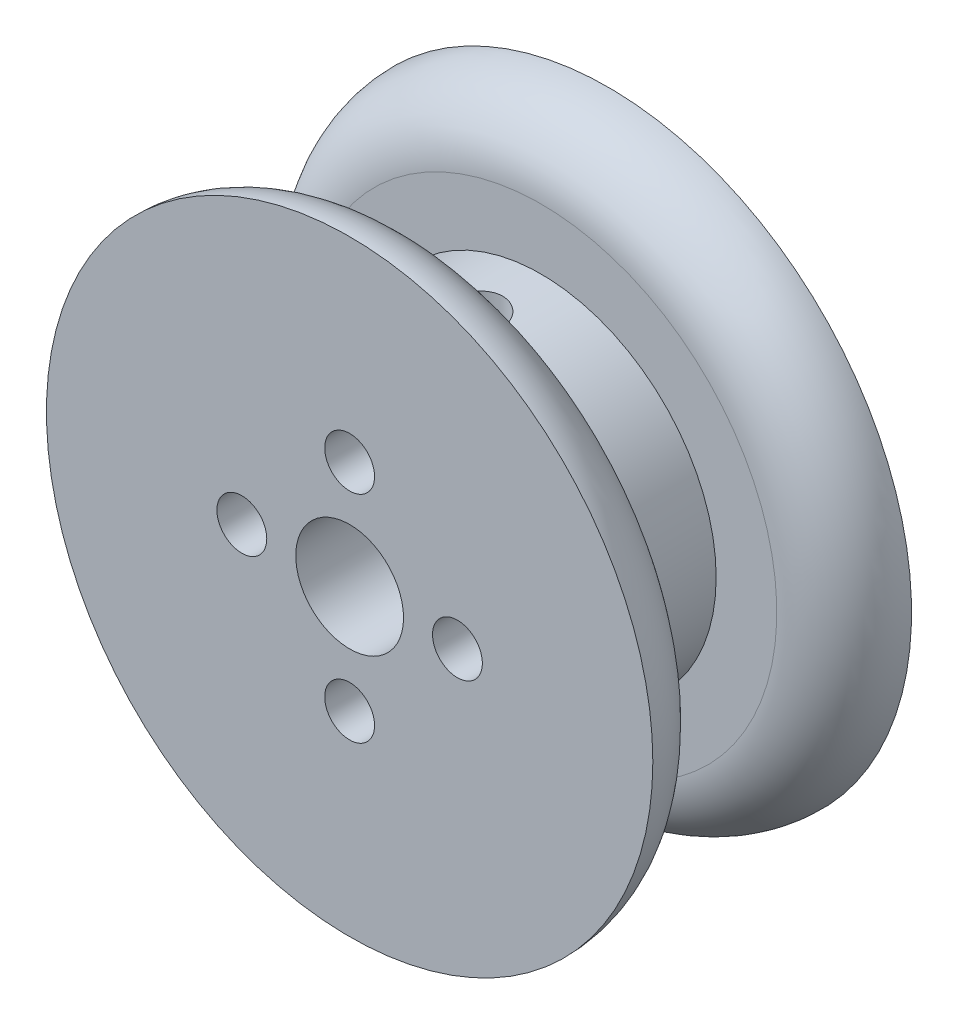
SolidWorks part; units mm, degrees
ref_plane "Front Plane" through (0, 0, 0) normal (0, 0, 1) x (1, 0, 0)
ref_plane "Top Plane" through (0, 0, 0) normal (0, 1, 0) x (1, 0, 0)
ref_plane "Right Plane" through (0, 0, 0) normal (1, 0, 0) x (0, 0, -1)
sketch "Sketch1" plane through (0, 0, 0) normal (0, 0, 1) x (1, 0, 0)
  circle A5 centre (0, 0) radius 22.5
  dimension "D1" = 45
extrude "Boss-Extrude1" add sketch "Sketch1" along normal blind 5
sketch "Sketch2" plane through (0, 0, 0) normal (0, 0, 1) x (1, 0, 0)
  circle A0 centre (0, 0) radius 13
  dimension "D1" = 26
extrude "Boss-Extrude2" add sketch "Sketch2" against normal blind 9.2
sketch "Sketch5" plane through (0, 0, -9.2) normal (0, 0, -1) x (-1, 0, 0)
  circle A2 centre (0, 0) radius 22.5
  circle A3 centre (0, 0) radius 22.5
  dimension "D1" = 0
extrude "Boss-Extrude4" add sketch "Sketch5" along normal blind 5
sketch "Sketch6" plane through (0, 0, 5) normal (0, 0, 1) x (1, 0, 0)
  line L0 (0, 0) -> (0, 8) construction
  circle A0 centre (0, 0) radius 4
  circle A1 centre (0, 8) radius 1.85
  circle A2 centre (8, 0) radius 1.85
  circle A3 centre (0, -8) radius 1.85
  circle A4 centre (-8, 0) radius 1.85
  point P14 (0, 0)
  dimension "D1" = 8
  dimension "D3" = 3.7
  dimension "D2" = 8
  dimension "D4" = 4
extrude "Cut-Extrude1" cut sketch "Sketch6" against normal through all
fillet "Fillet1" radius 5 2 edges at (22.5, 0, 0) (-22.5, 0, -9.2)
ref_plane "Plane1" through (0, 0, -14.2) normal (0, 0, -1) x (-1, 0, 0)
sketch "Sketch8" plane through (0, 0, 0) normal (0, 1, 0) x (1, 0, 0)
  line L0 (-4, -5) -> (4, -5) construction
  circle A0 centre (0, 4.5) radius 1.85
  point P2 (-0.1305, 3.763)
  point P3 (-0.1253, 5.3765)
  point P4 (0, 5.0318)
  point P5 (0, 4.1385)
  dimension "D1" = 3.7
  dimension "D2" = 9.5
extrude "Cut-Extrude2" cut sketch "Sketch8" against normal blind 26 and the other way blind 26
